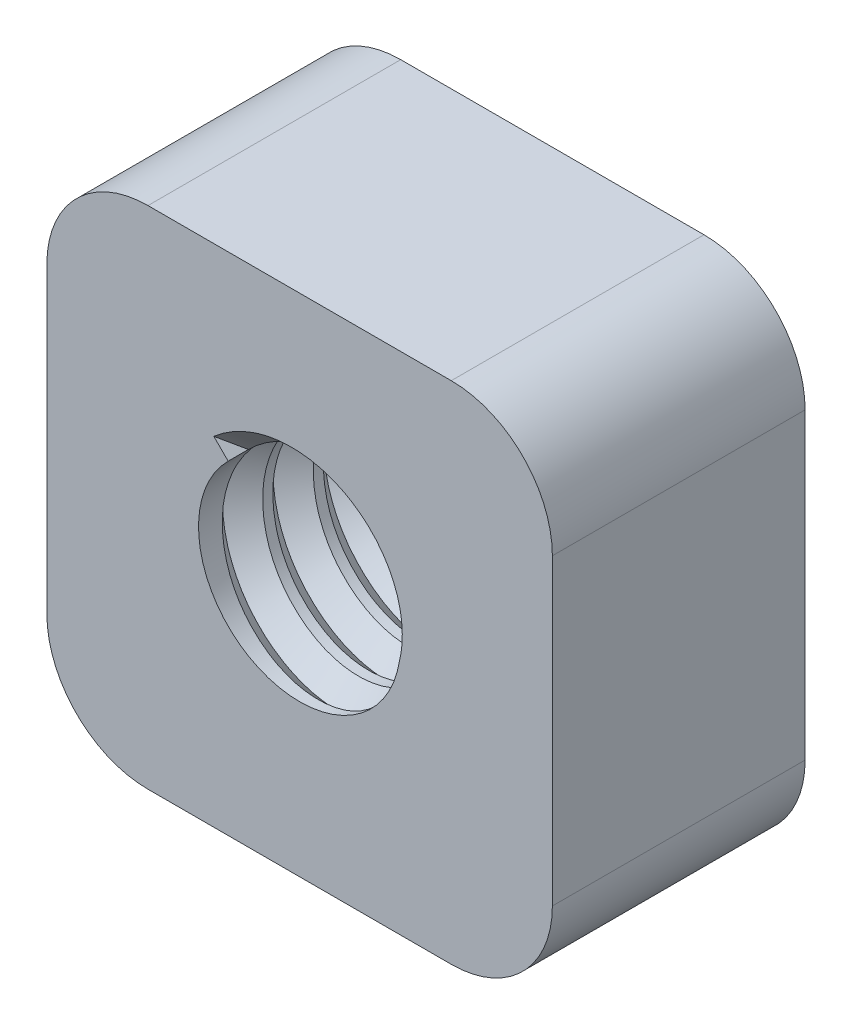
SolidWorks part; units mm, degrees
ref_plane "前视基准面" through (0, 0, 0) normal (0, 0, 1) x (1, 0, 0)
ref_plane "上视基准面" through (0, 0, 0) normal (0, 1, 0) x (1, 0, 0)
ref_plane "右视基准面" through (0, 0, 0) normal (1, 0, 0) x (0, 0, -1)
sketch "草图1" plane through (0, 0, 0) normal (0, 0, 1) x (1, 0, 0)
  line L1 (-5, 5) -> (5, 5)
  line L2 (-5, 5) -> (-5, -5)
  line L3 (-5, -5) -> (5, -5)
  line L4 (5, 5) -> (5, -5)
  line L5 (-5, 5) -> (5, -5) construction
  line L6 (-5, -5) -> (5, 5) construction
  point P0 (0, 0)
  dimension "D1" = 10
  dimension "D2" = 10
extrude "凸台-拉伸1" add sketch "草图1" along normal blind 5
sketch "草图2" plane through (0, 0, 5) normal (0, 0, 1) x (1, 0, 0)
  circle A0 centre (0, 0) radius 2
  dimension "D1" = 4
extrude "切除-拉伸1" cut sketch "草图2" against normal through all
sketch "草图3" plane through (0, 0, 5) normal (0, 0, 1) x (1, 0, 0)
  circle A0 centre (0, 0) radius 2 construction
  circle A1 centre (0, 0) radius 2
curve "螺旋线/涡状线1" pitch 1 height 3.5 radius 2 centre (0, 0, 5) axis (0, 0, -1) start towards (-0.7071, 0.7071, 0)
sketch "草图4" plane through (0, 0, 0) normal (0, 1, 0) x (1, 0, 0)
  line L0 (2, -4.225) -> (2, -5.025)
  line L1 (2, -4.625) -> (2.4, -4.625) construction
  line L2 (2, -4.225) -> (2.4, -4.625)
  line L3 (2.4, -4.625) -> (2, -5.025)
  point P4 (2, -4.625)
  dimension "D1" = 0.8
  dimension "D2" = 0.4
sweep "切除-扫描1" cut profiles "草图4" path "螺旋线/涡状线1"
fillet "圆角1" radius 2 4 edges at (-5, 5, 2.5) (5, 5, 2.5) (5, -5, 2.5) (-5, -5, 2.5)
